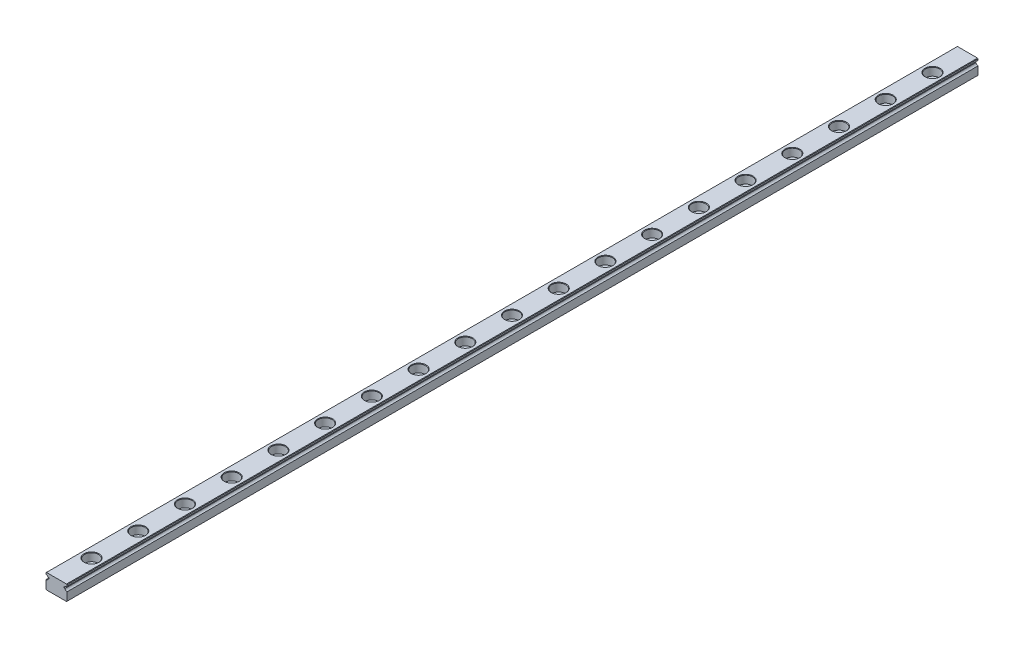
SolidWorks part; units mm, degrees
ref_plane "Спереди" through (0, 0, 0) normal (0, 0, 1) x (1, 0, 0)
ref_plane "Сверху" through (0, 0, 0) normal (0, 1, 0) x (1, 0, 0)
ref_plane "Справа" through (0, 0, 0) normal (1, 0, 0) x (0, 0, -1)
sketch "Sketch1" plane through (0, 0, 0) normal (0, 0, 1) x (1, 0, 0)
  line L0 (0, 0) -> (0, 4.3706) construction
  line L1 (-4.3, -3.25) -> (4.3, -3.25)
  line L2 (-4.5, -3.05) -> (-4.5, 0.455)
  line L3 (-4.3, 3.25) -> (4.3, 3.25)
  line L4 (4.5, -3.05) -> (4.5, 0.455)
  line L5 (-4.5, -3.25) -> (4.5, 3.25) construction
  line L6 (-4.5, 3.25) -> (4.5, -3.25) construction
  line L7 (-4.5, 2.445) -> (-4.5, 3.05)
  line L8 (4.5, 2.445) -> (4.5, 3.05)
  line L9 (-4.5, -3.05) -> (-4.3, -3.25)
  line L10 (4.3, -3.25) -> (4.5, -3.05)
  line L11 (4.3, 3.25) -> (4.5, 3.05)
  line L12 (-4.5, 3.05) -> (-4.3, 3.25)
  line L13 (3.6177, 1.2625) -> (3.1501, 1.2625)
  line L14 (-3.6177, 1.2625) -> (-3.1501, 1.2625)
  line L15 (3.1501, 1.2625) -> (3.1501, 1.7625)
  line L16 (-3.6501, 1.7625) -> (-3.1501, 1.7625)
  line L17 (-3.1501, 1.2625) -> (-3.1501, 1.7625)
  line L18 (3.6501, 1.7625) -> (3.1501, 1.7625)
  arc A0 (-4.5, 2.445) -> (-3.6501, 1.7625) centre (-4.6, 1.45) cw
  arc A1 (4.5, 2.445) -> (3.6501, 1.7625) centre (4.6, 1.45) ccw
  arc A2 (-3.6177, 1.2625) -> (-4.5, 0.455) centre (-4.6, 1.45) cw
  arc A3 (3.6177, 1.2625) -> (4.5, 0.455) centre (4.6, 1.45) ccw
  point P0 (0, 0)
  dimension "D4" = 1
  dimension "D5" = 0.1
  dimension "D1" = 9
  dimension "D2" = 6.5
  dimension "D3" = 1.8
  dimension "D6" = 0.5
  dimension "D7" = 0.5
extrude "Extrude1" add sketch "Sketch1" along normal blind 390
sketch "Sketch2" plane through (0, 3.25, 0) normal (0, 1, 0) x (1, 0, 0)
  line L0 (0, 0) -> (0, -15) construction
  circle A0 centre (0, -15) radius 1.75
  circle A1 centre (0, -15) radius 3
  dimension "D1" = 3.5
  dimension "D2" = 6
  dimension "D3" = 15
extrude "Extrude2" cut sketch "Sketch2" against normal up to next contours A0 region at (0, 3.25, 15)
extrude "Extrude4" cut sketch "Sketch" against normal blind 3.5
sketch "Sketch" plane through (0, 3.25, 0) normal (0, 1, 0) x (1, 0, 0) same geometry as "Sketch2"
chamfer "Chamfer1" distance 0.2 angle 45 2 edges at (0, -3.25, 16.75) (0, 3.25, 18)
pattern_linear "LPattern1" count 19 spacing 20 along (0, 0, 1) of "Extrude4", "Chamfer1", "Extrude2"
